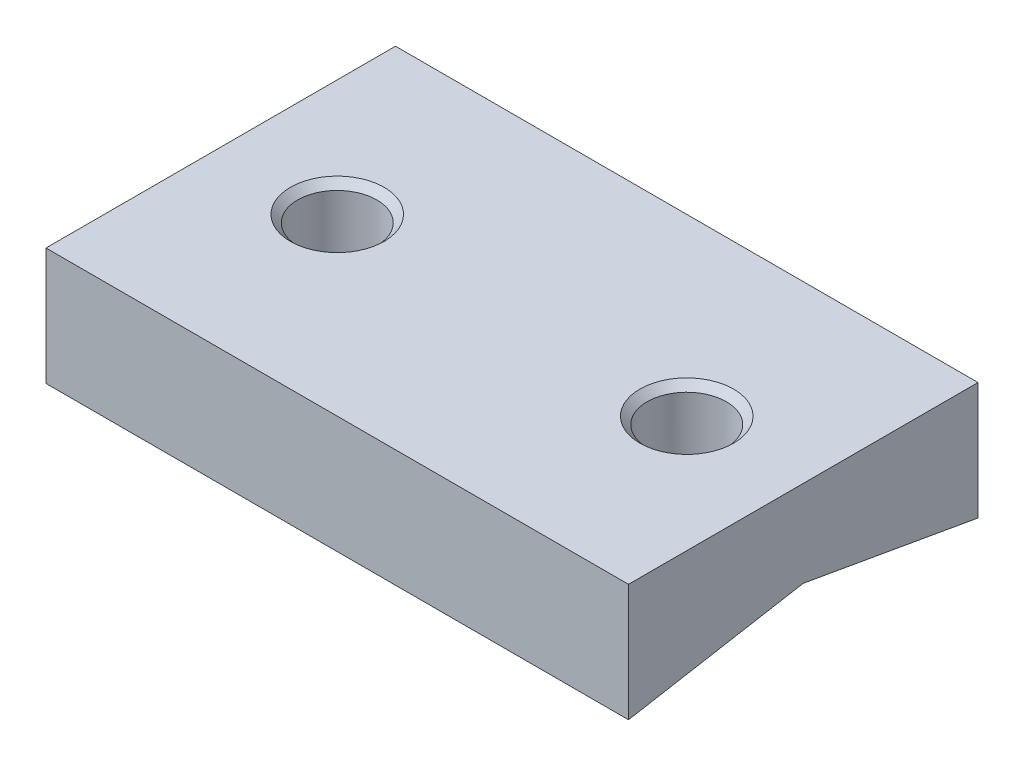
SolidWorks part; units mm, degrees
material "AISI 304"
ref_plane "Спереди" through (0, 0, 0) normal (0, 0, 1) x (1, 0, 0)
ref_plane "Сверху" through (0, 0, 0) normal (0, 1, 0) x (1, 0, 0)
ref_plane "Справа" through (0, 0, 0) normal (1, 0, 0) x (0, 0, -1)
ref_axis "Ось1" through (-62.9241, 0, 0) along (1, 0, 0)
sketch "Эскиз1" plane through (0, 0, 0) normal (0, 0, 1) x (1, 0, 0)
  line L0 (0, 0) -> (53, 0) construction
  line L1 (0, 100) -> (0, 0) construction
  line L2 (0, 102) -> (0.3488, 102)
  line L3 (0, 100) -> (0.3488, 100)
  line L4 (0, 102) -> (0, 100)
  line L5 (51, 0) -> (53, 0)
  line L6 (49.8785, 19.1) -> (51.8921, 19.1)
  arc A0 (0.3488, 102) -> (28.8538, 85.9935) centre (0.3488, 68.6154) cw
  arc A1 (28.8538, 85.9935) -> (53, 0) centre (-112.2, 0) cw
  arc A2 (0.3488, 100) -> (27.1461, 84.9524) centre (0.3488, 68.6154) cw
  arc A3 (27.1461, 84.9524) -> (51, 0) centre (-112.2, 0) cw
  point P0 (0, 101)
  dimension "D3" = 163.2
  dimension "D4" = 31.3846
  dimension "D1" = 204
  dimension "D6" = 38.2
  dimension "D5" = 53
  dimension "D2" = 2
ref_plane "Плоскость3" through (0, 105, 0) normal (0, 1, 0) x (1, 0, 0)
sketch "Эскиз2" plane through (0, 105, 0) normal (0, 1, 0) x (1, 0, 0)
  line L0 (-15, 0) -> (15, 0) construction
  line L2 (0, 15) -> (0, 0) construction
  line L4 (-25, 15) -> (25, 15)
  line L5 (-25, 15) -> (-25, -15)
  line L6 (-25, -15) -> (25, -15)
  line L7 (25, 15) -> (25, -15)
  dimension "D1" = 50
  dimension "D2" = 30
  dimension "D3" = 30
extrude "Бобышка-Вытянуть1" add sketch "Эскиз2" along normal mid plane 12
hole_wizard "Отверстие обработанное метчиком M81" positions "Эскиз3" profile "Эскиз4" tap size "M8" standard "ISO" end condition through all
sketch "Эскиз3" plane through (0, 111, 0) normal (0, 1, 0) x (1, 0, 0)
  point P0 (15, 0)
  point P2 (-15, 0)
sketch "Эскиз4" plane through (15, 111, 0) normal (1, 0, 0) x (0, 0, 1)
  line L0 (0, 0) -> (0, 12)
  line L1 (0, 12) -> (3.4, 12)
  line L2 (3.4, 12) -> (3.4, 0.625)
  line L3 (3.4, 0.625) -> (4.025, 0)
  line L5 (4.025, 0) -> (0, 0)
  line L6 (-3.4, 0.625) -> (-4.025, 0) construction
  line L11 (0, -6.35) -> (0, 107.95) construction
  dimension "Диаметр проходного сверла" = 6.8
  dimension "Глубина проходного сверла" = 12
  dimension "Диаметр передней зенковки" = 8.05
  dimension "Угол передней зенковки" = 90
cosmetic thread "Отверстие резьбы3" parameters "D2"=8
cosmetic thread "Отверстие резьбы4" parameters "D2"=8
sketch "Эскиз5" plane through (0, 0, 0) normal (1, 0, 0) x (0, 0, -1)
  line L0 (0, 0) -> (0, 102) construction
  line L1 (-34.0277, 97.5735) -> (0, 103.5735)
  line L2 (34.0277, 97.5735) -> (0, 103.5735)
  line L3 (-34.0277, 97.5735) -> (34.0277, 97.5735)
  circle A0 centre (0, 0) radius 102 construction
  dimension "D1" = 160
  dimension "D2" = 6
extrude "Вырез-Вытянуть1" cut sketch "Эскиз5" against normal through all and the other way through all
equation "\"D\"= 204мм"
equation "\"D1@Эскиз1\"=\"D\""
equation "\"D3@Эскиз1\"=\"D\"*0.8"
equation "\"D4@Эскиз1\"=\"D\"/6.5"
